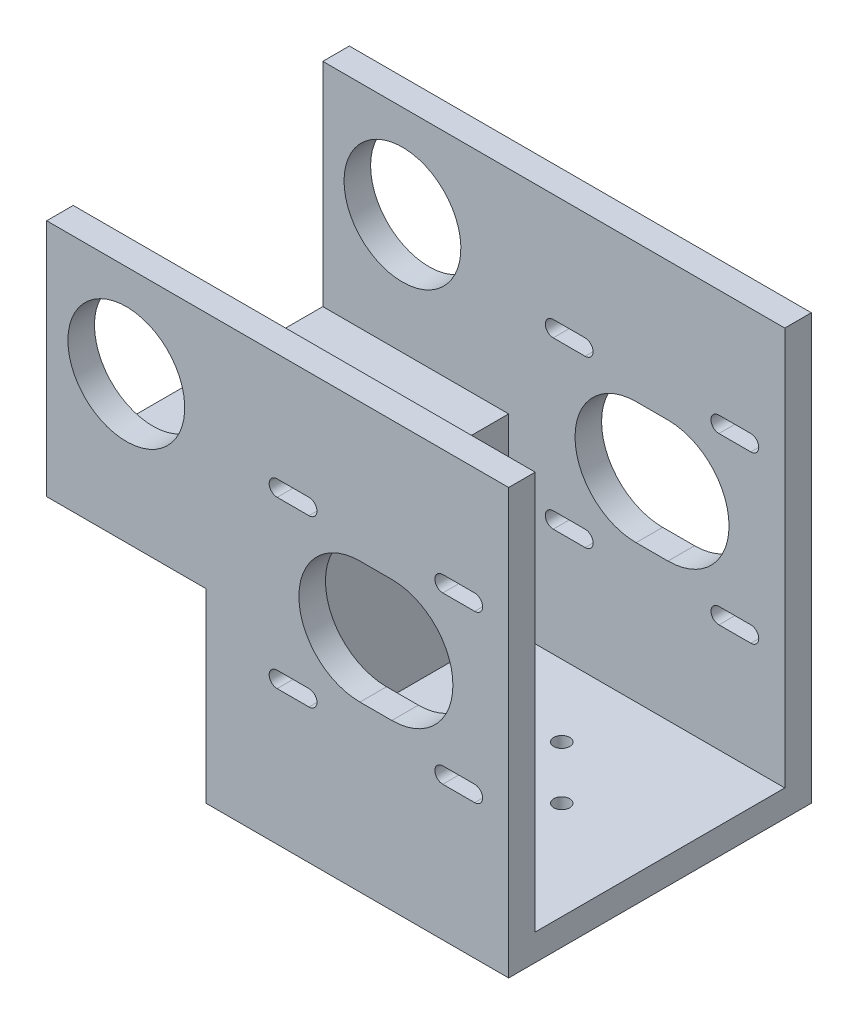
SolidWorks part; units mm, degrees
ref_plane "Front Plane" through (0, 0, 0) normal (0, 0, 1) x (1, 0, 0)
ref_plane "Top Plane" through (0, 0, 0) normal (0, 1, 0) x (1, 0, 0)
ref_plane "Right Plane" through (0, 0, 0) normal (1, 0, 0) x (0, 0, -1)
sketch "Sketch1" plane through (0, 0, 0) normal (0, 1, 0) x (1, 0, 0)
  line L1 (-28.5, 28.5) -> (28.5, 28.5)
  line L2 (-28.5, 28.5) -> (-28.5, -28.5)
  line L3 (-28.5, -28.5) -> (28.5, -28.5)
  line L4 (28.5, 28.5) -> (28.5, -28.5)
  line L5 (-28.5, 28.5) -> (28.5, -28.5) construction
  line L6 (-28.5, -28.5) -> (28.5, 28.5) construction
  point P0 (0, 0)
  dimension "D1" = 57
  dimension "D2" = 57
extrude "Boss-Extrude1" add sketch "Sketch1" along normal blind 80
sketch "Sketch3" plane through (28.5, 40, 0) normal (-1, 0, 0) x (0, 1, 0)
  line L1 (40, 23.5) -> (-35, 23.5)
  line L2 (40, 23.5) -> (40, -23.5)
  line L3 (40, -23.5) -> (-35, -23.5)
  line L4 (-35, 23.5) -> (-35, -23.5)
  line L5 (40, 23.5) -> (-35, -23.5) construction
  line L6 (40, -23.5) -> (-35, 23.5) construction
  line L10 (40, -28.5) -> (40, 28.5) construction
  line L11 (-40, -28.5) -> (-40, 28.5) construction
  line L12 (40, 28.5) -> (-40, 28.5) construction
  line L13 (40, -28.5) -> (-40, -28.5) construction
  point P0 (2.5, 0)
  dimension "D1" = 5
  dimension "D2" = 5
  dimension "D3" = 5
extrude "Cut-Extrude1" cut sketch "Sketch3" along normal blind 52
sketch "Sketch4" plane through (-40, 5, 0) normal (0, -1, 0) x (-1, 0, 0)
  line L0 (-40, 0) -> (-40, 10) construction
  circle A0 centre (-40, 0) radius 3.25
  circle A1 centre (-40, 10) radius 1.5
  circle A2 centre (-30, 0) radius 1.5
  circle A3 centre (-40, -10) radius 1.5
  circle A4 centre (-50, 0) radius 1.5
  point P0 (-10, 0)
  point P5 (0, 0)
  dimension "D1" = 6.5
  dimension "D2" = 3
  dimension "D3" = 10
  dimension "D4" = 4
extrude "Cut-Extrude2" cut sketch "Sketch4" along normal through all
sketch "Sketch7" plane through (-28.5, 0, 0) normal (-1, 0, 0) x (0, 0, 1)
  line L0 (28.5, 80) -> (28.5, 0) construction
  line L1 (-28.5, 80) -> (-23.5, 80)
  line L2 (-28.5, 80) -> (-28.5, 35)
  line L4 (-23.5, 80) -> (-23.5, 40)
  line L5 (28.5, 80) -> (23.5, 80)
  line L6 (28.5, 80) -> (28.5, 35)
  line L8 (23.5, 80) -> (23.5, 40)
  line L9 (-28.5, 80) -> (28.5, 80) construction
  line L11 (-23.5, 40) -> (23.5, 40)
  line L13 (-28.5, 35) -> (28.5, 35)
  point P2 (28.5, 45.9519)
  point P15 (-28.5, 45.759)
  dimension "D1" = 5
  dimension "D2" = 40
  dimension "D3" = 5
extrude "Boss-Extrude2" add sketch "Sketch7" along normal blind 30
sketch "Sketch8" plane through (-28.5, 0, 0) normal (-1, 0, 0) x (0, 0, 1)
  line L4 (-23.5, 80) -> (-23.5, 40)
  line L5 (-23.5, 40) -> (23.5, 40)
  line L6 (23.5, 40) -> (23.5, 80)
  line L7 (23.5, 80) -> (-23.5, 80)
  line L8 (-23.5, 80) -> (-23.5, 40)
  line L9 (-23.5, 40) -> (23.5, 40)
  line L10 (23.5, 40) -> (23.5, 80)
  line L11 (23.5, 80) -> (-23.5, 80)
  dimension "D1" = 0
extrude "Cut-Extrude5" cut sketch "Sketch8" against normal up to next
sketch "Sketch5" plane through (0, 0, -28.5) normal (0, 0, -1) x (-1, 0, 0)
  line L0 (-3.5, 42.5) -> (31.0759, 42.5) construction
  line L1 (-3.5, 42.5) -> (-3.5, 17.143) construction
  line L2 (-28.5, 80) -> (58.5, 80) construction
  line L3 (-28.5, 80) -> (58.5, 80) construction
  line L4 (58.5, 80) -> (58.5, 35) construction
  line L5 (-22.1, 58.1) -> (-16.1, 58.1) construction
  line L6 (-22.1, 59.6) -> (-16.1, 59.6)
  line L7 (-22.1, 56.6) -> (-16.1, 56.6)
  line L8 (-28.5, 80) -> (-28.5, 0) construction
  line L9 (-0.5, 42.5) -> (-6.5, 42.5) construction
  line L10 (-0.5, 31) -> (-6.5, 31)
  line L11 (-0.5, 54) -> (-6.5, 54)
  line L12 (-22.1, 26.9) -> (-16.1, 26.9) construction
  line L13 (-22.1, 25.4) -> (-16.1, 25.4)
  line L14 (-22.1, 28.4) -> (-16.1, 28.4)
  line L15 (15.1, 26.9) -> (9.1, 26.9) construction
  line L16 (15.1, 25.4) -> (9.1, 25.4)
  line L17 (15.1, 28.4) -> (9.1, 28.4)
  line L18 (15.1, 58.1) -> (9.1, 58.1) construction
  line L19 (15.1, 59.6) -> (9.1, 59.6)
  line L20 (15.1, 56.6) -> (9.1, 56.6)
  circle A5 centre (43.5, 62.5) radius 11
  arc A7 (-22.1, 59.6) -> (-22.1, 56.6) centre (-22.1, 58.1) ccw
  arc A8 (-16.1, 56.6) -> (-16.1, 59.6) centre (-16.1, 58.1) ccw
  arc A9 (-0.5, 31) -> (-0.5, 54) centre (-0.5, 42.5) ccw
  arc A10 (-6.5, 54) -> (-6.5, 31) centre (-6.5, 42.5) ccw
  arc A11 (-22.1, 25.4) -> (-22.1, 28.4) centre (-22.1, 26.9) cw
  arc A12 (-16.1, 28.4) -> (-16.1, 25.4) centre (-16.1, 26.9) cw
  arc A13 (15.1, 25.4) -> (15.1, 28.4) centre (15.1, 26.9) ccw
  arc A14 (9.1, 28.4) -> (9.1, 25.4) centre (9.1, 26.9) ccw
  arc A15 (15.1, 59.6) -> (15.1, 56.6) centre (15.1, 58.1) cw
  arc A16 (9.1, 56.6) -> (9.1, 59.6) centre (9.1, 58.1) cw
  point P2 (-19.1, 58.1)
  point P8 (-19.1, 42.5)
  point P13 (-3.5, 42.5)
  point P31 (-19.1, 26.9)
  point P38 (12.1, 26.9)
  point P45 (12.1, 58.1)
  dimension "D5" = 15.6
  dimension "D8" = 6
  dimension "D9" = 22
  dimension "D2" = 1.5
  dimension "D7" = 11.5
  dimension "D12" = 25
  dimension "D3" = 15.6
  dimension "D4" = 6
  dimension "D6" = 37.5
  dimension "D10" = 17.5
  dimension "D11" = 15
extrude "Cut-Extrude3" cut sketch "Sketch5" against normal through all
